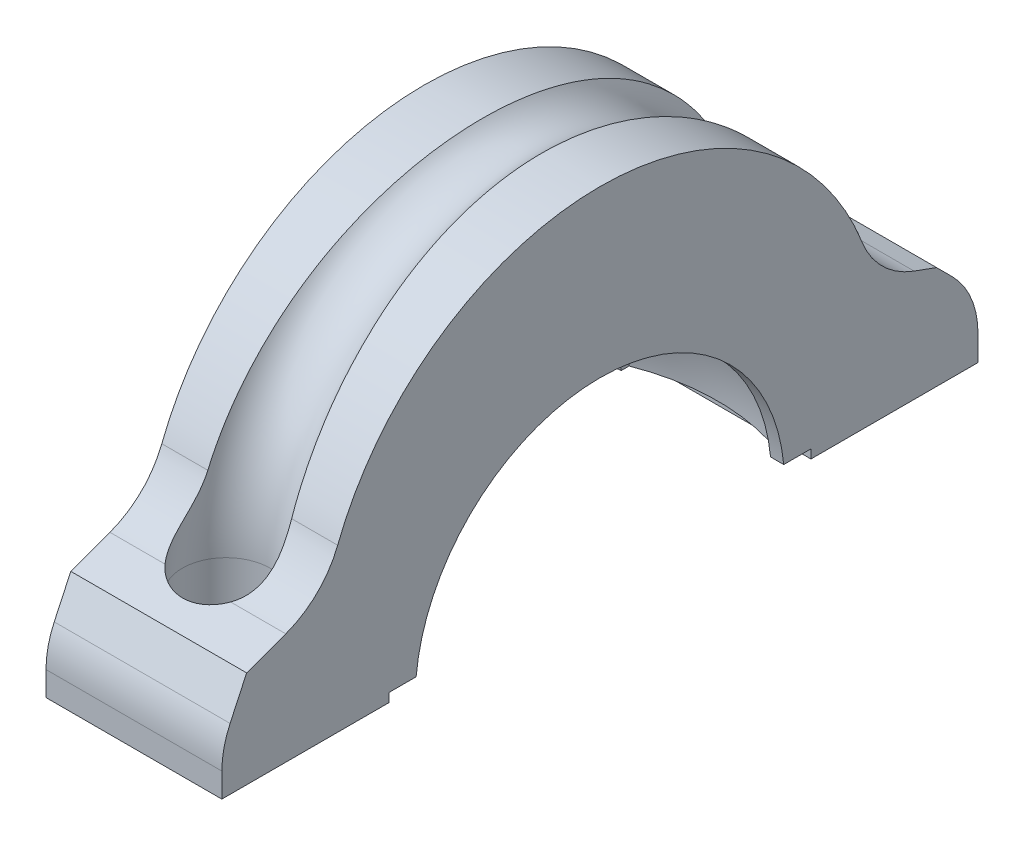
SolidWorks part; units mm, degrees
ref_plane "Front Plane" through (0, 0, 0) normal (0, 0, 1) x (1, 0, 0)
ref_plane "Top Plane" through (0, 0, 0) normal (0, 1, 0) x (1, 0, 0)
ref_plane "Right Plane" through (0, 0, 0) normal (1, 0, 0) x (0, 0, -1)
sketch "Sketch1" plane through (0, 0, 0) normal (1, 0, 0) x (0, 0, -1)
  line L0 (-86, 0) -> (-67, 0)
  line L1 (0, 0) -> (0, 10)
  line L2 (0, 10) -> (-11.8895, 14.3274)
  line L3 (-43, 17.5) -> (-43, 45.3769) construction
  line L4 (-86, 0) -> (-86, 10)
  line L5 (-86, 10) -> (-74.1105, 14.3274)
  line L6 (-19, 0) -> (-19, 1)
  line L8 (-67, 0) -> (-67, 1)
  line L10 (-19, 0) -> (0, 0)
  line L11 (-67, 1) -> (-19, 1)
  line L12 (-67, 0) -> (-19, 0) construction
  arc A1 (-74.1105, 14.3274) -> (-11.8895, 14.3274) centre (-43, 6.835) cw
  point P3 (0, 0)
  point P13 (0, 0)
  point P14 (-40, 6.835)
  dimension "D1" = 32
  dimension "D2" = 86
  dimension "D3" = 10
  dimension "D4" = 70
  dimension "D6" = 1
  dimension "D8" = 19
  dimension "D9" = 43
extrude "Boss-Extrude1" add sketch "Sketch1" along normal blind 20
fillet "Fillet1" radius 10 2 edges at (10, 14.3274, 11.8895) (10, 14.3274, 74.1105)
chamfer "Chamfer1" distance 3 angle 45 2 edges at (10, 10, 0) (10, 10, 86) first distance on face at (10, 5, 0) first distance on face at (10, 11.3231, 82.3648)
fillet "Fillet2" [suppressed] radius 1
fillet "Fillet3" [suppressed] radius 1
ref_plane "Plane1" through (10, 0, 0) normal (1, 0, 0) x (0, 0, -1)
sketch "Sketch2" plane through (10, 0, 0) normal (1, 0, 0) x (0, 0, -1)
  line L1 (-10.5, -11.403) -> (-10.5, 10)
  line L4 (-43, -11.403) -> (-43, 46.1538) construction
  line L5 (-75.5, -11.403) -> (-75.5, 10)
  line L7 (-67, 1) -> (-19, 1) construction
  line L8 (-19, 0) -> (0, 0) construction
  arc A1 (-75.5, 10) -> (-10.5, 10) centre (-43, 10) cw
  point P11 (0, 0)
  point P12 (-43, 1)
  dimension "D2" = 32.5
  dimension "D1" = 65
  dimension "D3" = 10
ref_plane "Plane4" through (0, 0, 86) normal (0, 0, -1) x (-1, 0, 0)
ref_plane "Plane5" through (0, -11.403, 0) normal (0, -1, 0) x (-1, 0, 0)
sketch "Sketch5" plane through (0, -11.403, 0) normal (0, -1, 0) x (-1, 0, 0)
  circle A0 centre (-10, -10.5) radius 5
  point P3 (0, 0)
  dimension "D1" = 10
sweep "augu cut" cut profiles "Sketch5" path "Sketch2"
ref_plane "laagri center " through (0, -1, 0) normal (0, -1, 0) x (-1, 0, 0)
sketch "Sketch6" plane through (0, -1, 0) normal (0, -1, 0) x (1, 0, 0)
  line L0 (0, 64) -> (1.5, 64)
  line L2 (1.5, 64.9089) -> (1.5, 64)
  line L3 (0, 43) -> (20, 43)
  line L4 (18.5, 64.9089) -> (18.5, 64)
  line L5 (10, 10.5) -> (10, 75.5) construction
  line L7 (0, 67) -> (0, 19) construction
  line L8 (18.5, 64) -> (20, 64)
  line L9 (20, 67) -> (20, 19) construction
  line L10 (0, 64) -> (0, 43)
  line L12 (20, 64) -> (20, 43)
  arc A0 (1.5, 64.9089) -> (18.5, 64.9089) centre (10, 43) cw
  point P0 (10.2498, 50.9501)
  point P5 (-5.357, 37.6918)
  point P6 (10, 66.5)
  point P17 (0, 0)
  point P18 (-3.4829, 39.5659)
  point P19 (0, 0)
  point P21 (5.8187, 47.8105)
  point P22 (0, 0)
  point P24 (0, 0)
  dimension "D2" = 23.5
  dimension "D1" = 17
  dimension "D3" = 21
  dimension "D4" = 1.5
  dimension "D5" = 1.5
  dimension "D6" = 0.9089
revolve "Cut-Revolve2" cut sketch "Sketch6" angle 360 about L3
sketch "Sketch8" plane through (0, -1, 0) normal (0, -1, 0) x (-1, 0, 0)
  line L0 (-30.4774, -7.5) -> (-30.4774, -72.5) construction
  line L3 (-30.4774, -40) -> (16.6094, -40) construction
fillet "Fillet4" radius 10 2 edges at (10, 4.9805, 86) (10, 7, 0)
